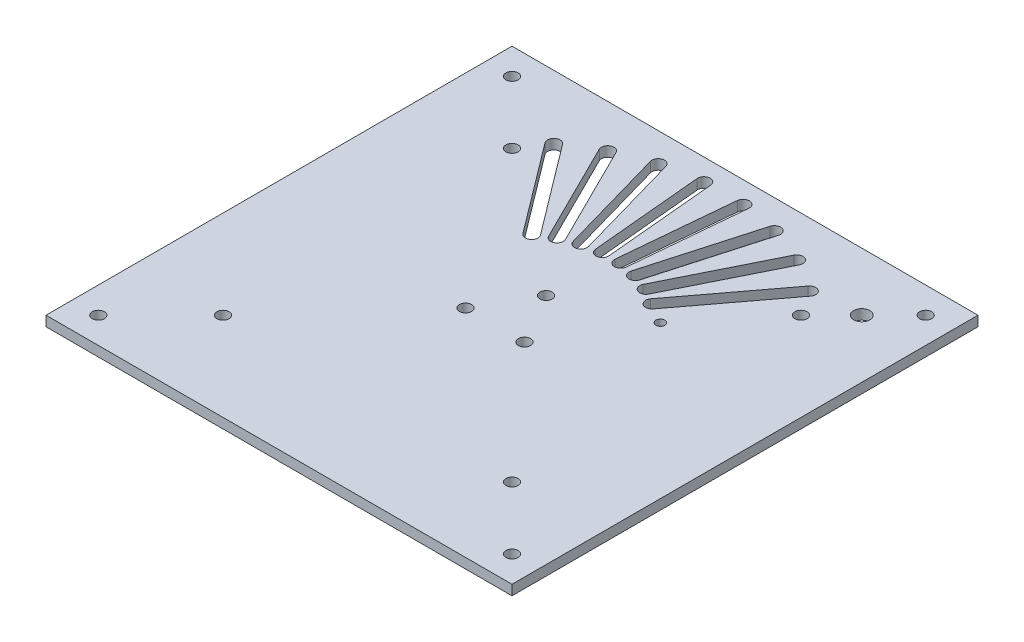
SolidWorks part; units mm, degrees
material "Acrylic (Medium-high impact)"
ref_plane "Front Plane" through (0, 0, 0) normal (0, 0, 1) x (1, 0, 0)
ref_plane "Top Plane" through (0, 0, 0) normal (0, 1, 0) x (1, 0, 0)
ref_plane "Right Plane" through (0, 0, 0) normal (1, 0, 0) x (0, 0, -1)
sketch "Sketch2" plane through (0, 0, 0) normal (0, 1, 0) x (1, 0, 0)
  line L1 (-65, -65) -> (65, -65)
  line L2 (-65, -65) -> (-65, 65)
  line L3 (-65, 65) -> (65, 65)
  line L4 (65, -65) -> (65, 65)
  line L5 (-65, -65) -> (65, 65) construction
  line L6 (-65, 65) -> (65, -65) construction
  point P0 (0, 0)
  dimension "D1" = 130
  dimension "D2" = 130
extrude "Boss-Extrude1" add sketch "Sketch2" along normal blind 2.8
sketch "Sketch4" plane through (0, 2.8, 0) normal (0, 1, 0) x (1, 0, 0)
  line L8 (57.7, -57.7) -> (57.7, 57.7)
  line L9 (57.7, 57.7) -> (-57.7, 57.7)
  line L10 (-57.7, 57.7) -> (-57.7, -57.7)
  line L11 (-57.7, -57.7) -> (57.7, -57.7)
  line L12 (57.7, -57.7) -> (57.7, 57.7) construction
  line L13 (57.7, 57.7) -> (-57.7, 57.7) construction
  line L14 (-57.7, 57.7) -> (-57.7, -57.7) construction
  line L15 (-57.7, -57.7) -> (57.7, -57.7) construction
  circle A0 centre (-57.7, 57.7) radius 1.7
  circle A1 centre (57.7, 57.7) radius 1.7
  circle A2 centre (57.7, -57.7) radius 1.7
  circle A3 centre (-57.7, -57.7) radius 1.7
  dimension "D2" = 3.4
  dimension "D1" = 7.3
extrude "Cut-Extrude1" cut sketch "Sketch4" against normal up to next
sketch "Sketch6" plane through (0, 2.8, 0) normal (0, 1, 0) x (1, 0, 0)
  line L6 (-40.3051, -40.3051) -> (40.3051, -40.3051) construction
  line L7 (-40.3051, -40.3051) -> (-40.3051, 40.3051) construction
  line L8 (-40.3051, 40.3051) -> (40.3051, 40.3051) construction
  line L9 (40.3051, -40.3051) -> (40.3051, 40.3051) construction
  line L10 (-40.3051, -40.3051) -> (40.3051, 40.3051) construction
  line L11 (-40.3051, 40.3051) -> (40.3051, -40.3051) construction
  circle A4 centre (-40.3051, 40.3051) radius 1.7
  circle A5 centre (40.3051, 40.3051) radius 1.7
  circle A6 centre (40.3051, -40.3051) radius 1.7
  circle A7 centre (-40.3051, -40.3051) radius 1.7
  point P0 (0, 0)
  dimension "D2" = 3.4
  dimension "D1" = 57
extrude "Cut-Extrude2" cut sketch "Sketch6" against normal up to next
sketch "Sketch8" plane through (0, 2.8, 0) normal (0, 1, 0) x (1, 0, 0)
  circle A4 centre (0, 9.5) radius 1.7
  circle A5 centre (8.2272, -4.75) radius 1.7
  circle A6 centre (-8.2272, -4.75) radius 1.7
  point P9 (0, 0)
  dimension "D1" = 9.5
  dimension "D3" = 3.4
  dimension "D2" = 3
extrude "Cut-Extrude3" cut sketch "Sketch8" against normal up to next
sketch "Sketch9" plane through (0, 2.8, 0) normal (0, 1, 0) x (1, 0, 0)
  line L0 (65, -65) -> (65, 65) construction
  line L1 (48.7904, 48.7904) -> (0, 0) construction
  line L2 (0, 0) -> (50000, 0) construction
  circle A0 centre (0, 0) radius 65 construction
  circle A1 centre (48.7904, 48.7904) radius 2.25
  dimension "D3" = 4
  dimension "D1" = 4.5
  dimension "D2" = 45
extrude "Primary wire hole" cut sketch "Sketch9" against normal up to next
sketch "Sketch10" plane through (0, 2.8, 0) normal (0, 1, 0) x (1, 0, 0)
  line L0 (0, 0) -> (22.5064, 18.8851) construction
  line L1 (0, 0) -> (50000, 0) construction
  circle A0 centre (0, 0) radius 24.13 construction
  circle A1 centre (22.5064, 18.8851) radius 1.25
  dimension "D1" = 48.26
  dimension "D3" = 2.5
  dimension "D2" = 40
  dimension "D4" = 4
extrude "Secondary wire hole" cut sketch "Sketch10" against normal up to next
sketch "Sketch11" plane through (0, 2.8, 0) normal (0, 1, 0) x (1, 0, 0)
  line L0 (-35.6575, 47.3192) -> (-16.7786, 22.266) construction
  line L1 (-34.2599, 48.3723) -> (-15.381, 23.3191)
  line L2 (-37.0552, 46.266) -> (-18.1762, 21.2128)
  line L3 (0, 0) -> (-16.7786, 22.266) construction
  line L4 (-27.9382, 52.2789) -> (-13.976, 24.1874)
  line L5 (-24.804, 53.8367) -> (-10.8418, 25.7452)
  line L6 (-26.3711, 53.0578) -> (-12.4089, 24.9663) construction
  line L7 (-17.8729, 56.5171) -> (-9.3013, 26.3409)
  line L8 (-14.5061, 57.4735) -> (-5.9345, 27.2972)
  line L9 (-16.1895, 56.9953) -> (-7.6179, 26.8191) construction
  line L10 (-7.2008, 58.8368) -> (-4.3109, 27.6002)
  line L11 (-3.7157, 59.1593) -> (-0.8258, 27.9227)
  line L12 (-5.4582, 58.9981) -> (-2.5684, 27.7614) construction
  line L13 (3.7157, 59.1593) -> (0.8258, 27.9227)
  line L14 (7.2008, 58.8368) -> (4.3109, 27.6002)
  line L15 (5.4582, 58.9981) -> (2.5684, 27.7614) construction
  line L18 (0, 0) -> (50000, 0) construction
  line L19 (14.5061, 57.4735) -> (5.9345, 27.2972)
  line L20 (17.8729, 56.5171) -> (9.3013, 26.3409)
  line L21 (16.1895, 56.9953) -> (7.6179, 26.8191) construction
  line L22 (24.804, 53.8367) -> (10.8418, 25.7452)
  line L23 (27.9382, 52.2789) -> (13.976, 24.1874)
  line L24 (26.3711, 53.0578) -> (12.4089, 24.9663) construction
  line L25 (34.2599, 48.3723) -> (15.381, 23.3191)
  line L26 (37.0552, 46.266) -> (18.1762, 21.2128)
  line L27 (35.6575, 47.3192) -> (16.7786, 22.266) construction
  line L28 (0, 0) -> (16.7786, 22.266) construction
  circle A0 centre (0, 0) radius 24.13 construction
  circle A1 centre (0, 0) radius 63 construction
  arc A2 (-34.2599, 48.3723) -> (-37.0552, 46.266) centre (-35.6575, 47.3192) ccw
  arc A3 (-18.1762, 21.2128) -> (-15.381, 23.3191) centre (-16.7786, 22.266) ccw
  arc A4 (-24.804, 53.8367) -> (-27.9382, 52.2789) centre (-26.3711, 53.0578) ccw
  arc A5 (-13.976, 24.1874) -> (-10.8418, 25.7452) centre (-12.4089, 24.9663) ccw
  arc A6 (-14.5061, 57.4735) -> (-17.8729, 56.5171) centre (-16.1895, 56.9953) ccw
  arc A7 (-9.3013, 26.3409) -> (-5.9345, 27.2972) centre (-7.6179, 26.8191) ccw
  arc A8 (-3.7157, 59.1593) -> (-7.2008, 58.8368) centre (-5.4582, 58.9981) ccw
  arc A9 (-4.3109, 27.6002) -> (-0.8258, 27.9227) centre (-2.5684, 27.7614) ccw
  arc A10 (7.2008, 58.8368) -> (3.7157, 59.1593) centre (5.4582, 58.9981) ccw
  arc A11 (0.8258, 27.9227) -> (4.3109, 27.6002) centre (2.5684, 27.7614) ccw
  arc A14 (17.8729, 56.5171) -> (14.5061, 57.4735) centre (16.1895, 56.9953) ccw
  arc A15 (5.9345, 27.2972) -> (9.3013, 26.3409) centre (7.6179, 26.8191) ccw
  arc A16 (27.9382, 52.2789) -> (24.804, 53.8367) centre (26.3711, 53.0578) ccw
  arc A17 (10.8418, 25.7452) -> (13.976, 24.1874) centre (12.4089, 24.9663) ccw
  arc A18 (37.0552, 46.266) -> (34.2599, 48.3723) centre (35.6575, 47.3192) ccw
  arc A19 (15.381, 23.3191) -> (18.1762, 21.2128) centre (16.7786, 22.266) ccw
  point P6 (-26.2181, 34.7926)
  point P17 (-19.39, 39.012)
  point P24 (-11.9037, 41.9072)
  point P31 (-4.0133, 43.3797)
  point P36 (0, 0)
  point P38 (4.0133, 43.3797)
  point P48 (11.9037, 41.9072)
  point P55 (19.39, 39.012)
  point P62 (26.2181, 34.7926)
  dimension "D1" = 48.26
  dimension "D2" = 126
  dimension "D4" = 2
  dimension "D5" = 3.5
  dimension "D7" = 53
  dimension "D8" = 53
  dimension "D6" = 8
extrude "Cut-Extrude6" cut sketch "Sketch11" against normal up to next
equation "\"D1@Sketch4\"=4.50+2.8"
equation "\"D1@Sketch10\"=1.9in"
equation "\"D1@Sketch11\"=1.9in"
equation "\"D2@Sketch11\"=130mm-2*2mm"
